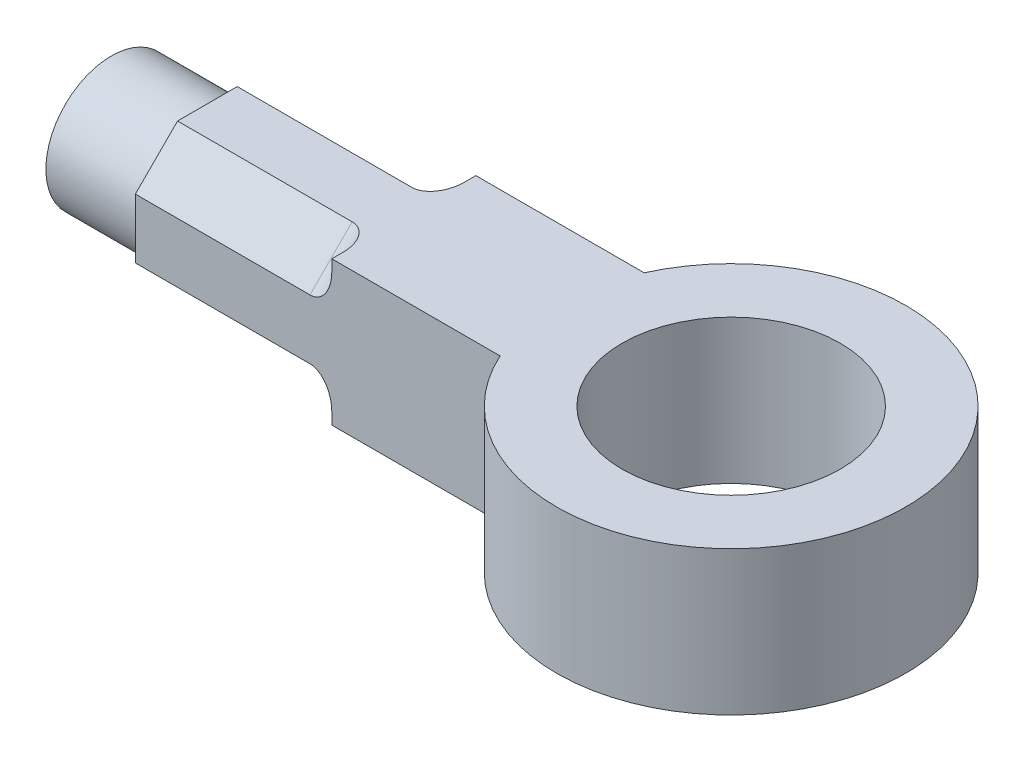
SolidWorks part; units mm, degrees
ref_plane "Front Plane" through (0, 0, 0) normal (0, 0, 1) x (1, 0, 0)
ref_plane "Top Plane" through (0, 0, 0) normal (0, 1, 0) x (1, 0, 0)
ref_plane "Right Plane" through (0, 0, 0) normal (1, 0, 0) x (0, 0, -1)
sketch "Sketch1" plane through (0, 0, 0) normal (0, 1, 0) x (1, 0, 0)
  circle A0 centre (0, 0) radius 25
  circle A1 centre (0, 0) radius 40
  dimension "D1" = 80
  dimension "D2" = 50
extrude "Boss-Extrude1" add sketch "Sketch1" along normal mid plane 36
ref_plane "Plane1" through (-120, 0, 0) normal (1, 0, 0) x (0, 0, -1)
sketch "Sketch2" plane through (-120, 0, 0) normal (1, 0, 0) x (0, 0, -1)
  line L1 (-16.5, 6.8345) -> (-16.5, -6.8345)
  line L2 (-16.5, -6.8345) -> (-6.8345, -16.5)
  line L3 (-6.8345, -16.5) -> (6.8345, -16.5)
  line L4 (6.8345, -16.5) -> (16.5, -6.8345)
  line L5 (16.5, -6.8345) -> (16.5, 6.8345)
  line L6 (16.5, 6.8345) -> (6.8345, 16.5)
  line L7 (6.8345, 16.5) -> (-6.8345, 16.5)
  line L8 (-6.8345, 16.5) -> (-16.5, 6.8345)
  circle A0 centre (0, 0) radius 16.5 construction
extrude "Boss-Extrude2" add sketch "Sketch2" along normal blind 45 separate body
sketch "Sketch3" plane through (-120, 0, 0) normal (1, 0, 0) x (0, 0, -1)
  circle A0 centre (0, 0) radius 15
extrude "Boss-Extrude3" add sketch "Sketch3" against normal blind 22
sketch "Sketch4" plane through (-75, 0, 0) normal (1, 0, 0) x (0, 0, -1)
  line L1 (16.5, 16.5) -> (-16.5, 16.5)
  line L2 (16.5, 16.5) -> (16.5, -16.5)
  line L3 (16.5, -16.5) -> (-16.5, -16.5)
  line L4 (-16.5, 16.5) -> (-16.5, -16.5)
  line L5 (16.5, 16.5) -> (-16.5, -16.5) construction
  line L6 (16.5, -16.5) -> (-16.5, 16.5) construction
  point P0 (0, 0)
  dimension "D1" = 33
  dimension "D2" = 33
extrude "Boss-Extrude4" add sketch "Sketch4" along normal up to next
fillet "Fillet1" radius 5 4 edges at (-75, -11.6673, 11.6673) (-75, -11.6673, -11.6673) (-75, 11.6673, 11.6673) (-75, 11.6673, -11.6673)
fillet "Fillet7" radius 1.5 2 edges at (-40, 16.5, 0) (-40, -16.5, 0)
scale "Scala2" scale about centroid uniform scaling yes scale factor 0.1
sketch "Schizzo3" plane through (0, 1.8, 0) normal (0, 1, 0) x (1, 0, 0)
  line L1 (-42.2376, 5.1541) -> (-28.8467, 5.1541)
  line L2 (-42.2376, 5.1541) -> (-42.2376, -7.039)
  line L3 (-42.2376, -7.039) -> (-28.8467, -7.039)
  line L4 (-28.8467, 5.1541) -> (-28.8467, -7.039)
extrude "Taglio-Estrusione3" cut sketch "Schizzo3" against normal up to surface (0.15 mm away) up to face at (-43.8327, 1.65, 0)
sketch "Schizzo4" plane through (0, -1.8, 0) normal (0, -1, 0) x (1, 0, 0)
  line L1 (-29.8481, 5.1934) -> (-47.4211, 5.1934)
  line L2 (-29.8481, 5.1934) -> (-29.8481, -6.8623)
  line L3 (-29.8481, -6.8623) -> (-47.4211, -6.8623)
  line L4 (-47.4211, 5.1934) -> (-47.4211, -6.8623)
extrude "Taglio-Estrusione4" cut sketch "Schizzo4" against normal up to surface (0.15 mm away) up to face at (-43.8327, -1.65, 0)
